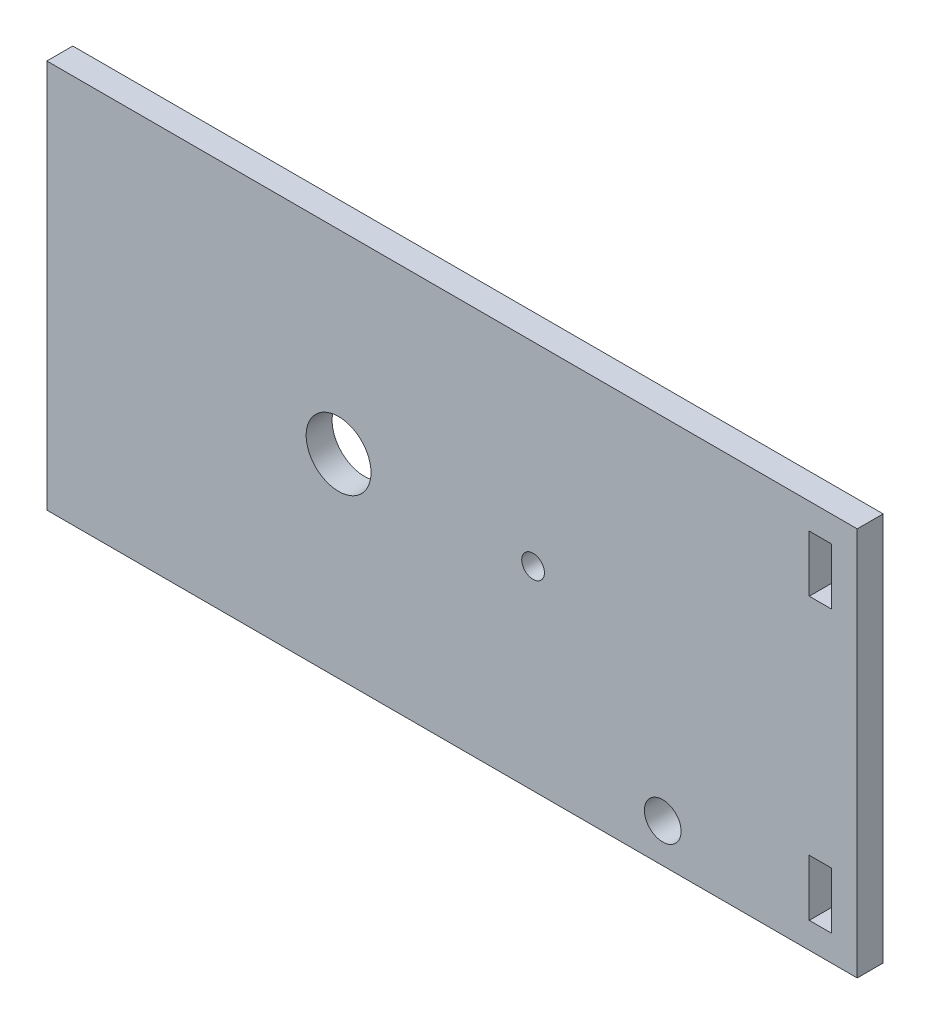
SolidWorks part; units mm, degrees
ref_plane "Front Plane" through (0, 0, 0) normal (0, 0, 1) x (1, 0, 0)
ref_plane "Top Plane" through (0, 0, 0) normal (0, 1, 0) x (1, 0, 0)
ref_plane "Right Plane" through (0, 0, 0) normal (1, 0, 0) x (0, 0, -1)
sketch "Sketch1" plane through (0, 0, 0) normal (0, 0, 1) x (1, 0, 0)
  line L1 (-81, -30) -> (40, -30)
  line L2 (-81, -30) -> (-81, 30)
  line L3 (-81, 30) -> (40, 30)
  line L11 (40, 30) -> (40, -30)
  circle A3 centre (-36, 0) radius 5
  circle A4 centre (14, -24) radius 2.83
  point P9 (-81, 0)
  dimension "D3" = 121
  dimension "D4" = 5.66
  dimension "D5" = 6
  dimension "D6" = 10
  dimension "D7" = 95
  dimension "D8" = 76
  dimension "D2" = 60
  dimension "D10" = 0
  dimension "D11" = 45
extrude "Boss-Extrude1" add sketch "Sketch1" along normal blind 4
sketch "Sketch2" plane through (0, 0, 0) normal (0, 0, 1) x (1, 0, 0)
  line L0 (40, -30) -> (44, -30)
  line L1 (44, -30) -> (44, 30)
  line L2 (44, 30) -> (40, 30)
  line L4 (40, 30) -> (-81, 30) construction
  line L16 (40, 30) -> (40, -30)
  dimension "D1" = 4
extrude "Boss-Extrude2" add sketch "Sketch2" along normal blind 4
sketch "Sketch3" plane through (0, 0, 0) normal (0, 0, 1) x (1, 0, 0)
  line L0 (40, 30) -> (40, -30) construction
  line L1 (40, 26) -> (36.6, 26)
  line L2 (40, 26) -> (40, 17.3)
  line L3 (40, 17.3) -> (36.6, 17.3)
  line L4 (36.6, 26) -> (36.6, 17.3)
  line L5 (-81, -30) -> (40, -30) construction
  line L6 (40, -17.3) -> (36.6, -17.3)
  line L7 (40, -17.3) -> (40, -26)
  line L8 (40, -26) -> (36.6, -26)
  line L9 (36.6, -17.3) -> (36.6, -26)
  line L10 (-81, 30) -> (40, 30) construction
  circle A0 centre (-6, 0) radius 1.75
  circle A1 centre (-36, 0) radius 5 construction
  dimension "D1" = 3.5
  dimension "D2" = 30
  dimension "D3" = 4
  dimension "D4" = 4
  dimension "D5" = 3.4
  dimension "D6" = 8.7
extrude "Cut-Extrude1" cut sketch "Sketch3" along normal through all both and the other way through all
equation "\"hole_width\"=3.4"
equation "\"D5@Sketch3\"=\"hole_width\""
equation "\"hole_length\"=8.7"
equation "\"D6@Sketch3\"=\"hole_length\""
